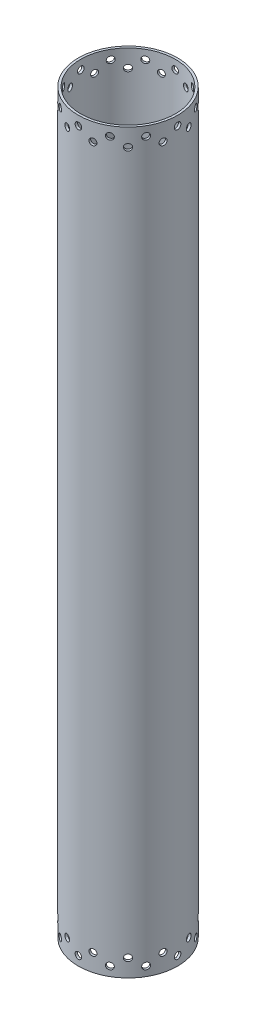
SolidWorks part; units mm, degrees
material "6061-T6 (SS)"
ref_plane "Front Plane" through (0, 0, 0) normal (0, 0, 1) x (1, 0, 0)
ref_plane "Top Plane" through (0, 0, 0) normal (0, 1, 0) x (1, 0, 0)
ref_plane "Right Plane" through (0, 0, 0) normal (1, 0, 0) x (0, 0, -1)
sketch "Sketch2" plane through (0, 0, 0) normal (0, 1, 0) x (1, 0, 0)
  circle A0 centre (0, 0) radius 76.2
  circle A1 centre (0, 0) radius 72.5932
  dimension "D1" = 152.4
  dimension "D2" = 145.1864
extrude "Boss-Extrude1" add sketch "Sketch2" along normal blind 1130.3
sketch "Sketch3" plane through (0, 0, 0) normal (0, 0, 1) x (1, 0, 0)
  line L0 (0, 1130.3) -> (0, 1116.203) construction
  line L1 (72.5932, 1130.3) -> (-72.5932, 1130.3) construction
  circle A0 centre (0, 1116.203) radius 5.0419
  dimension "D1" = 10.0838
  dimension "D2" = 14.097
extrude "Cut-Extrude1" cut sketch "Sketch3" against normal blind 1143
ref_plane "Plane1" through (-19.722, 0, 73.6035) normal (-0.2588, 0, 0.9659) x (0, -1, 0)
sketch "Sketch6" plane through (-19.722, 0, 73.6035) normal (-0.2588, 0, 0.9659) x (0, -1, 0)
  line L0 (-1130.3, 0) -> (-1103.503, 0) construction
  line L1 (-1130.3, 76.2) -> (-1130.3, -76.2) construction
  circle A0 centre (-1103.503, 0) radius 5.0419
  dimension "D1" = 10.0838
  dimension "D2" = 26.797
extrude "Cut-Extrude2" cut sketch "Sketch6" against normal blind 25.4
pattern_circular "CirPattern2" count 12 over 360 about axis through (0, 1130.3, 0) along (0, -1, 0) of "Cut-Extrude2", "Cut-Extrude1"
ref_plane "Plane2" through (0, 565.15, 0) normal (0, 1, 0) x (1, 0, 0)
mirror "Mirror1" about plane through (0, 565.15, 0) normal (0, 1, 0) of "CirPattern2"
equation "\"holeDia\"=0.397"
equation "\"D1@Sketch3\"=\"holeDia\""
equation "\"D1@Sketch6\"=\"holeDia\""
equation "\"numHoles\"=12"
equation "\"D1@CirPattern2\"=\"numHoles\""
equation "\"D1@Plane1\"=180/\"numHoles\""
equation "\"D2@Sketch6\"=\"D2@Sketch3\"+0.5"
